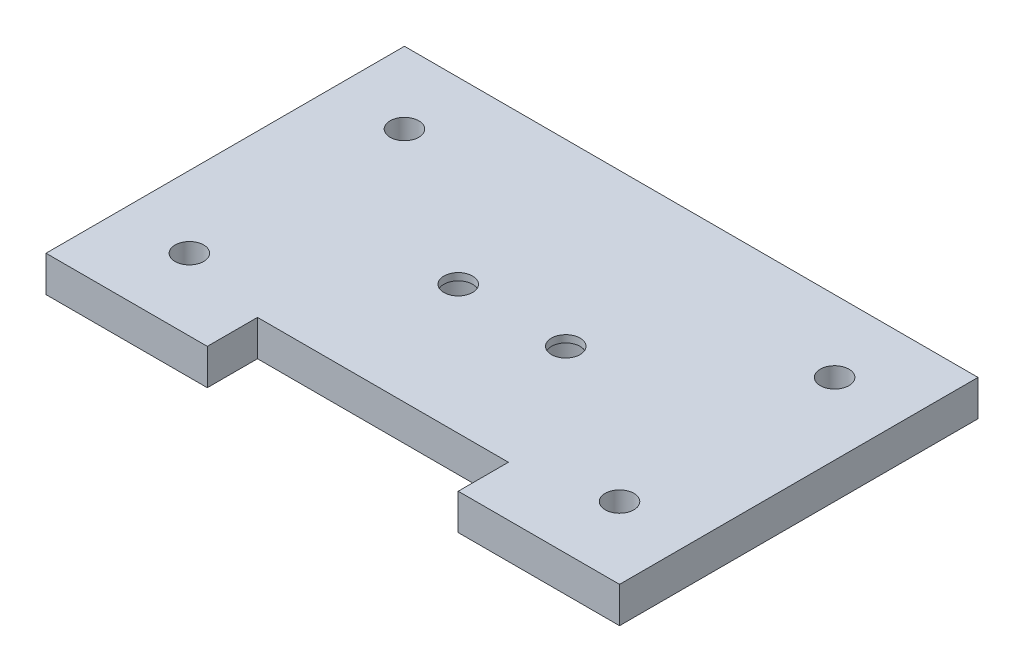
SolidWorks part; units mm, degrees
ref_plane "Front Plane" through (0, 0, 0) normal (0, 0, 1) x (1, 0, 0)
ref_plane "Top Plane" through (0, 0, 0) normal (0, 1, 0) x (1, 0, 0)
ref_plane "Right Plane" through (0, 0, 0) normal (1, 0, 0) x (0, 0, -1)
sketch "Sketch1" plane through (0, 0, 0) normal (0, 1, 0) x (1, 0, 0)
  line L0 (-17.5, -25) -> (17.5, -25)
  line L1 (-40, 25) -> (40, 25)
  line L2 (-40, 25) -> (-40, -25)
  line L3 (-40, -25) -> (40, -25)
  line L4 (40, 25) -> (40, -25)
  line L5 (-40, 25) -> (40, -25) construction
  line L6 (-40, -25) -> (40, 25) construction
  line L7 (-17.5, -25) -> (-17.5, -18)
  line L8 (17.5, -25) -> (17.5, -18)
  line L9 (-17.5, -18) -> (17.5, -18)
  line L10 (0, 25) -> (0, -25) construction
  line L11 (0, -18) -> (0, -25) construction
  circle A0 centre (-30, 15) radius 2
  circle A1 centre (30, 15) radius 2
  circle A2 centre (30, -15) radius 2
  circle A3 centre (-30, -15) radius 2
  point P0 (0, 0)
  point P24 (0, 0)
  point P26 (0, 0)
  dimension "D3" = 4
  dimension "D1" = 80
  dimension "D2" = 50
  dimension "D4" = 10
  dimension "D5" = 10
  dimension "D8" = 30
  dimension "D9" = 60
  dimension "D10" = 7
  dimension "D11" = 35
  dimension "D6" = 2
  dimension "D7" = 2
extrude "Boss-Extrude1" add sketch "Sketch1" along normal blind 5 contours L7 L9 L8 L3 L4 L1 L2 A3 A2 A1 A0 region at (0, 0, -1.4218)
sketch "Sketch2" plane through (0, 0, 0) normal (0, -1, 0) x (1, 0, 0)
  line L0 (-7.5, 0) -> (7.5, 0) construction
  circle A0 centre (-7.5, 0) radius 4
  circle A1 centre (7.5, 0) radius 4
  circle A2 centre (-7.5, 0) radius 2
  circle A3 centre (7.5, 0) radius 2
  point P4 (0, 0)
  dimension "D2" = 8
  dimension "D3" = 8
  dimension "D4" = 4
  dimension "D5" = 4
  dimension "D1" = 15
extrude "Cut-Extrude1" cut sketch "Sketch2" against normal blind 4 contours A2 | A2 A0 | A3 | A1 A3 region at (-11.3869, 0, 0) region at (3.6131, 0, 0) region at (-7.5, 0, 0) region at (7.5, 0, 0)
extrude "Cut-Extrude2" cut sketch "Sketch2<4>" against normal through all contours A2 | A3 region at (-7.5, 0, 0) region at (7.5, 0, 0)
sketch "Sketch2<4>" plane through (0, 0, 0) normal (0, -1, 0) x (1, 0, 0) same geometry as "Sketch2"
